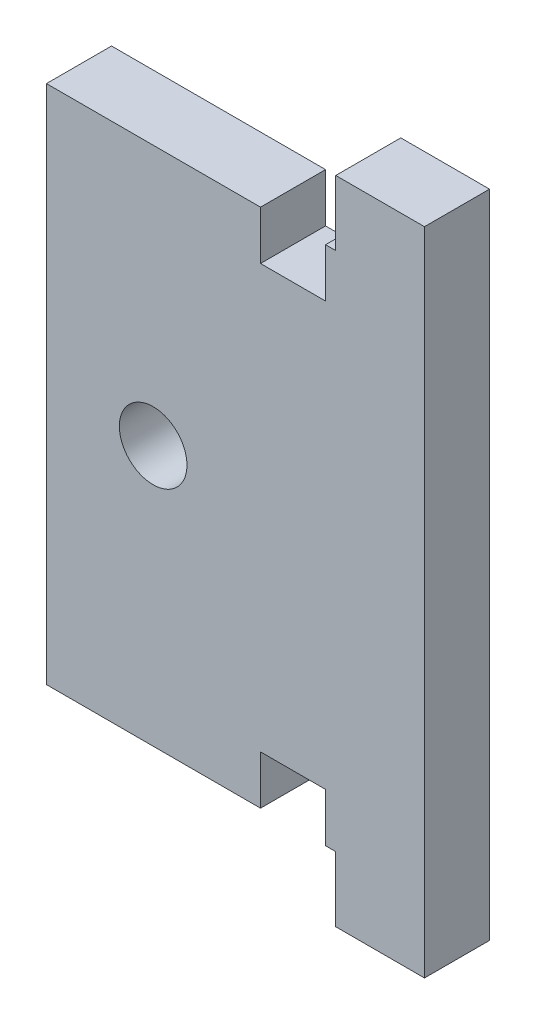
SolidWorks part; units mm, degrees
material "AISI 4130 Steel, annealed at 865C"
ref_plane "X-Y Datum" through (0, 0, 0) normal (0, 0, 1) x (1, 0, 0)
ref_plane "X-Z Datum" through (0, 0, 0) normal (0, 1, 0) x (1, 0, 0)
ref_plane "Y-Z Datum" through (0, 0, 0) normal (1, 0, 0) x (0, 0, -1)
sketch "Sketch2" plane through (0, 0, 0) normal (0, 0, 1) x (1, 0, 0)
  line L0 (32.9006, 127) -> (0, 127) construction
  line L1 (0, 0) -> (43.942, 0)
  line L2 (0, 0) -> (0, 127)
  line L3 (0, 127) -> (43.942, 127)
  line L4 (43.942, 0) -> (43.942, 127)
  point P7 (17.4625, 31.75)
  point P8 (17.4625, 95.25)
  dimension "D1" = 43.942
extrude "Boss-Extrude1" add sketch "Sketch2" along normal blind 6.35
hole_wizard "M6 Clearance Hole1" positions "Sketch3" profile "Sketch4" hole size "M6" standard "ANSI Metric" end condition through all
sketch "Sketch3" plane through (0, 0, 6.35) normal (0, 0, 1) x (1, 0, 0)
  point P0 (17.4625, 31.75)
  point P3 (17.4625, 95.25)
sketch "Sketch4" plane through (17.4625, 31.75, 6.35) normal (1, 0, 0) x (0, -1, 0)
  line L0 (0, 0) -> (0, 6.35)
  line L1 (0, 6.35) -> (3.3, 6.35)
  line L2 (3.3, 6.35) -> (3.3, 0)
  line L5 (3.3, 0) -> (0, 0)
  line L11 (0, -6.35) -> (0, 107.95) construction
  dimension "Thru Hole Dia." = 6.6
  dimension "Thru Hole Depth" = 6.35
sketch "Sketch5" plane through (0, 0, 6.35) normal (0, 0, 1) x (1, 0, 0)
  line L0 (7.0505, 127) -> (7.0505, 0)
  line L1 (43.942, 127) -> (0, 127) construction
  line L2 (0, 0) -> (43.942, 0) construction
  circle A0 centre (17.4625, 95.25) radius 3.3 construction
  point P6 (14.1625, 95.25)
  line M4 (0, 127) -> (0, 0)
  line M5 (0, 0) -> (43.942, 0)
  line M7 (43.942, 127) -> (0, 127)
  dimension "D1" = 7.112
extrude "Cut-Extrude1" cut sketch "Sketch5" against normal through all and the other way through all contours L0 M7 M4 M5 region at (3.5253, 63.5, 6.35)
sketch "Sketch6" plane through (0, 0, 6.35) normal (0, 0, 1) x (1, 0, 0)
  line L0 (-3.175, 120.65) -> (36.0756, 120.65)
  line L1 (36.0756, 120.65) -> (36.0756, 130.175)
  line L2 (36.0756, 130.175) -> (-3.175, 130.175)
  line L3 (-3.175, 130.175) -> (-3.175, 120.65)
  line L4 (0, 123.825) -> (32.9006, 123.825)
  line L5 (32.9006, 123.825) -> (32.9006, 127)
  line L6 (32.9006, 127) -> (0, 127)
  line L7 (0, 127) -> (0, 123.825)
  line L8 (0, 123.825) -> (32.9006, 123.825)
  line L9 (32.9006, 123.825) -> (32.9006, 127)
  line L10 (32.9006, 127) -> (0, 127)
  line L11 (0, 127) -> (0, 123.825)
  line L12 (0, 60.325) -> (32.9006, 60.325)
  line L13 (32.9006, 60.325) -> (32.9006, 63.5)
  line L14 (32.9006, 63.5) -> (0, 63.5)
  line L15 (0, 63.5) -> (0, 60.325)
  line L16 (0, 60.325) -> (32.9006, 60.325)
  line L17 (32.9006, 60.325) -> (32.9006, 63.5)
  line L18 (32.9006, 63.5) -> (0, 63.5)
  line L19 (0, 63.5) -> (0, 60.325)
  line L24 (0, 0) -> (34.925, 0)
  line L25 (34.925, 0) -> (34.925, 3.175)
  line L26 (34.925, 3.175) -> (0, 3.175)
  line L27 (0, 3.175) -> (0, 0)
  line L28 (36.0756, 66.675) -> (-3.175, 66.675)
  line L29 (-3.175, 66.675) -> (-3.175, 57.15)
  line L30 (-3.175, 57.15) -> (36.0756, 57.15)
  line L31 (36.0756, 57.15) -> (36.0756, 66.675)
  line L32 (38.1, 6.35) -> (-3.175, 6.35)
  line L33 (-3.175, 6.35) -> (-3.175, -3.175)
  line L34 (-3.175, -3.175) -> (38.1, -3.175)
  line L35 (38.1, -3.175) -> (38.1, 6.35)
  line L36 (35.2819, 127) -> (35.2819, 0)
  line L37 (43.942, 127) -> (7.0505, 127) construction
  line L38 (7.0505, 0) -> (43.942, 0) construction
  line M19 (7.0505, 127) -> (7.0505, 0)
  line M20 (7.0505, 0) -> (43.942, 0)
  line M22 (43.942, 127) -> (7.0505, 127)
  dimension "D5" = 2.3813
  dimension "D1" = 0
  dimension "D2" = 0
  dimension "D4" = 3.175
extrude "Cut-Extrude2" cut sketch "Sketch6" against normal through all contours L36 L9 L8 L0 M22 M19 | L8 L9 M22 M19 | L36 L28 L18 L17 L16 L30 M19 | L17 L18 L16 M19 | L36 L32 L26 L25 M19 M20 | L25 L26 M19 M20 region at (22.1716, 122.4845, 6.35) region at (19.9756, 125.4125, 6.35) region at (21.1662, 66.3771, 6.35) region at (19.9756, 61.9125, 6.35) region at (21.3402, 4.7229, 6.35) region at (20.9878, 1.5875, 6.35)
sketch "Sketch7" plane through (0, 0, 6.35) normal (0, 0, 1) x (1, 0, 0)
  line L18 (34.29, 120.65) -> (27.94, 120.65)
  line L19 (34.29, 120.65) -> (34.29, 115.8875)
  line L20 (34.29, 115.8875) -> (27.94, 115.8875)
  line L21 (27.94, 120.65) -> (27.94, 115.8875)
  line L22 (34.29, 71.4375) -> (27.94, 71.4375)
  line L23 (34.29, 71.4375) -> (34.29, 66.675)
  line L24 (34.29, 66.675) -> (27.94, 66.675)
  line L25 (27.94, 71.4375) -> (27.94, 66.675)
  line L26 (34.29, 57.15) -> (27.94, 57.15)
  line L27 (34.29, 57.15) -> (34.29, 52.3875)
  line L28 (34.29, 52.3875) -> (27.94, 52.3875)
  line L29 (27.94, 57.15) -> (27.94, 52.3875)
  line L30 (34.29, 11.1125) -> (27.94, 11.1125)
  line L31 (34.29, 11.1125) -> (34.29, 6.35)
  line L32 (34.29, 6.35) -> (27.94, 6.35)
  line L33 (27.94, 11.1125) -> (27.94, 6.35)
  point P6 (0, 0)
  point P11 (0, 0)
extrude "Cut-Extrude3" cut sketch "Sketch7" against normal through all
sketch "Sketch8" plane through (0, 0, 6.35) normal (0, 0, 1) x (1, 0, 0)
  line L0 (34.925, 63.5) -> (43.942, 63.5)
  line L1 (43.942, 0) -> (43.942, 127) construction
  circle M3 centre (17.4625, 95.25) radius 3.3
  line M4 (35.2819, 120.65) -> (34.29, 120.65)
  line M5 (34.29, 120.65) -> (34.29, 115.8875)
  line M6 (34.29, 115.8875) -> (27.94, 115.8875)
  line M7 (27.94, 115.8875) -> (27.94, 120.65)
  line M8 (27.94, 120.65) -> (7.0505, 120.65)
  line M9 (7.0505, 120.65) -> (7.0505, 66.675)
  line M10 (7.0505, 66.675) -> (27.94, 66.675)
  line M11 (27.94, 66.675) -> (27.94, 71.4375)
  line M12 (27.94, 71.4375) -> (34.29, 71.4375)
  line M13 (34.29, 71.4375) -> (34.29, 66.675)
  line M14 (34.29, 66.675) -> (35.2819, 66.675)
  line M15 (35.2819, 66.675) -> (35.2819, 57.15)
  line M29 (43.942, 0) -> (43.942, 127)
  line M30 (43.942, 127) -> (35.2819, 127)
  line M31 (35.2819, 127) -> (35.2819, 120.65)
extrude "Cut-Extrude4" cut sketch "Sketch8" against normal through all and the other way through all contours L0 M15 M29 M30 M31 M4 M5 M6 M7 M8 M9 M10 M11 M12 M13 M14 M3 region at (26.0518, 94.0762, 6.35)
